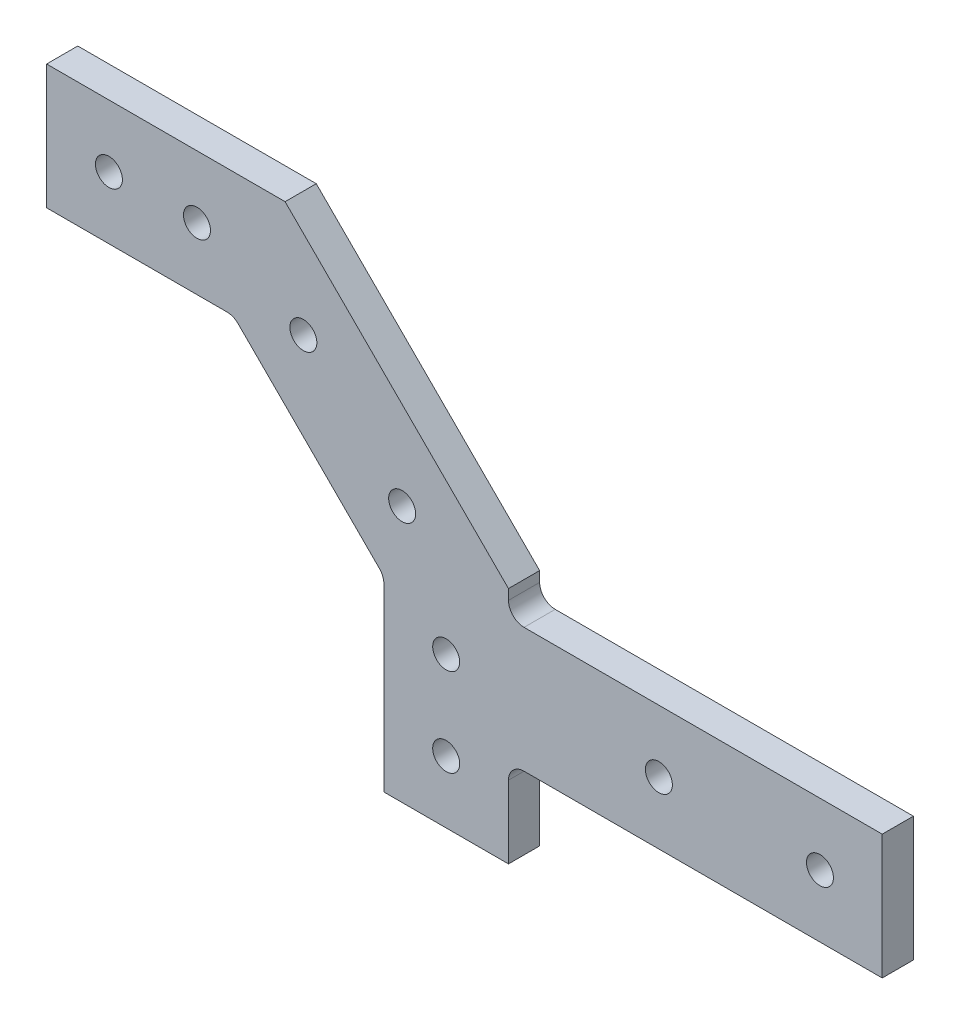
SolidWorks part; units mm, degrees
material "6061-T6 (SS)"
ref_plane "Front" through (0, 0, 0) normal (0, 0, 1) x (1, 0, 0)
ref_plane "Top" through (0, 0, 0) normal (0, 1, 0) x (1, 0, 0)
ref_plane "Right" through (0, 0, 0) normal (1, 0, 0) x (0, 0, -1)
sketch "Sketch4" plane through (-304.8, 0, 0) normal (0, 0, 1) x (1, 0, 0)
  line L0 (317.5, 63.5) -> (317.5, 0)
  line L2 (317.5, 63.5) -> (279.4, 101.6)
  line L4 (279.4, 101.6) -> (-279.4, 101.6)
  line L5 (317.5, 0) -> (-317.5, 0) construction
  line L6 (-279.4, 101.6) -> (-317.5, 63.5)
  line L7 (-317.5, 63.5) -> (-317.5, -25.4)
sketch "Sketch1" plane through (0, 0, 0) normal (0, 0, 1) x (1, 0, 0)
  line L0 (0, 38.1) -> (0, 58.2395)
  line L1 (25.4, 63.5) -> (101.6, 63.5)
  line L2 (101.6, 63.5) -> (101.6, 38.1)
  line L3 (101.6, 38.1) -> (25.4, 38.1)
  line L6 (0, 58.2395) -> (-30.6605, 88.9)
  line L7 (-30.6605, 88.9) -> (-68.7605, 88.9)
  line L8 (-68.7605, 88.9) -> (-68.7605, 114.3)
  line L9 (-68.7605, 114.3) -> (-20.1395, 114.3)
  line L10 (-20.1395, 114.3) -> (25.4, 68.7605)
  line L11 (25.4, 68.7605) -> (25.4, 63.5)
  line L12 (0, 38.1) -> (0, 0) construction
  line L13 (12.7, 63.5) -> (-25.4, 101.6) construction
  line L14 (-25.4, 101.6) -> (-584.2, 101.6) construction
  line L15 (25.4, 63.5) -> (0, 63.5) construction
  line L16 (0, 63.5) -> (0, 58.2395) construction
  line L17 (25.4, 38.1) -> (25.4, 20.1395)
  line L18 (25.4, 20.1395) -> (0, 20.1395)
  line L19 (0, 20.1395) -> (0, 38.1)
  line L20 (25.4, 38.1) -> (0, 38.1) construction
  dimension "D1" = 38.1
  dimension "D2" = 25.4
  dimension "D3" = 38.1
  dimension "D4" = 101.6
  dimension "D5" = 12.7
  dimension "D6" = 12.7
  dimension "D7" = 12.7
  dimension "D8" = 12.7
  dimension "D9" = 38.1
extrude "Boss-Extrude1" add sketch "Sketch1" along normal blind 6.35
fillet "Fillet1" radius 3.175 4 edges at (-30.6605, 88.9, 3.175) (0, 58.2395, 3.175) (25.4, 63.5, 3.175) (25.4, 38.1, 3.175)
hole_wizard "M5 Clearance Hole1" positions "Sketch2" profile "Sketch3" hole size "M5" standard "ANSI Metric"
sketch "Sketch2" plane through (0, 0, 6.35) normal (0, 0, 1) x (1, 0, 0)
  line L5 (101.6, 63.5) -> (88.9, 50.8) construction
  line L6 (88.9, 50.8) -> (101.6, 38.1) construction
  line L8 (88.9, 50.8) -> (56.0612, 50.8) construction
  line L12 (56.0612, 50.8) -> (12.7, 50.8) construction
  line L14 (-68.7605, 114.3) -> (-56.0605, 101.6) construction
  line L15 (-56.0605, 101.6) -> (-68.7605, 88.9) construction
  line L17 (-56.0605, 101.6) -> (-38.1, 101.6) construction
  line L19 (-16.4197, 92.6197) -> (3.7197, 72.4803) construction
  line L21 (25.4, 68.7605) -> (-20.1395, 114.3) construction
  line L22 (25.4, 20.1395) -> (12.7, 32.8395) construction
  line L23 (12.7, 32.8395) -> (0, 20.1395) construction
  line L25 (12.7, 32.8395) -> (12.7, 50.8) construction
  point P0 (12.7, 50.8)
  point P4 (56.0612, 50.8)
  point P6 (88.9, 50.8)
  point P44 (3.7197, 72.4803)
  point P46 (-16.4197, 92.6197)
  point P48 (-38.1, 101.6)
  point P50 (-56.0605, 101.6)
  point P87 (12.7, 32.8395)
  point P90 (0, 0)
  dimension "D1" = 12.7
  dimension "D2" = 12.7
  dimension "D3" = 12.7
  dimension "D4" = 12.7
sketch "Sketch3" plane through (12.7, 50.8, 6.35) normal (1, 0, 0) x (0, -1, 0)
  line L0 (0, 0) -> (0, 20.4024)
  line L1 (0, 20.4024) -> (2.75, 18.75)
  line L2 (2.75, 18.75) -> (2.75, 0)
  line L5 (2.75, 0) -> (0, 0)
  line L10 (0, 20.4024) -> (-2.75, 18.75) construction
  line L11 (0, -6.35) -> (0, 107.95) construction
  dimension "Hole Dia." = 5.5
  dimension "Hole Depth" = 18.75
  dimension "Drill Angle" = 118
